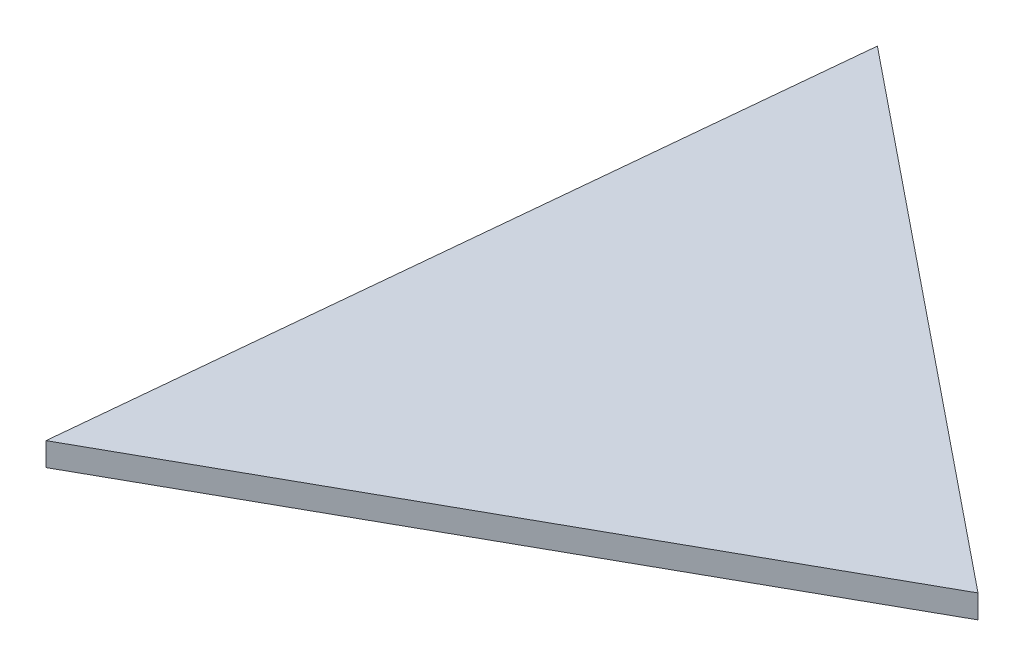
SolidWorks part; units mm, degrees
ref_plane "前视基准面" through (0, 0, 0) normal (0, 0, 1) x (1, 0, 0)
ref_plane "上视基准面" through (0, 0, 0) normal (0, 1, 0) x (1, 0, 0)
ref_plane "右视基准面" through (0, 0, 0) normal (1, 0, 0) x (0, 0, -1)
sketch "草图1" plane through (0, 0, 0) normal (0, 1, 0) x (1, 0, 0)
  line L0 (0, 0) -> (51.1847, 28.5984)
  line L1 (51.1847, 28.5984) -> (6.3371, 64.8339)
  line L2 (6.3371, 64.8339) -> (0, 0)
extrude "凸台-拉伸1" add sketch "草图1" along normal blind 2
